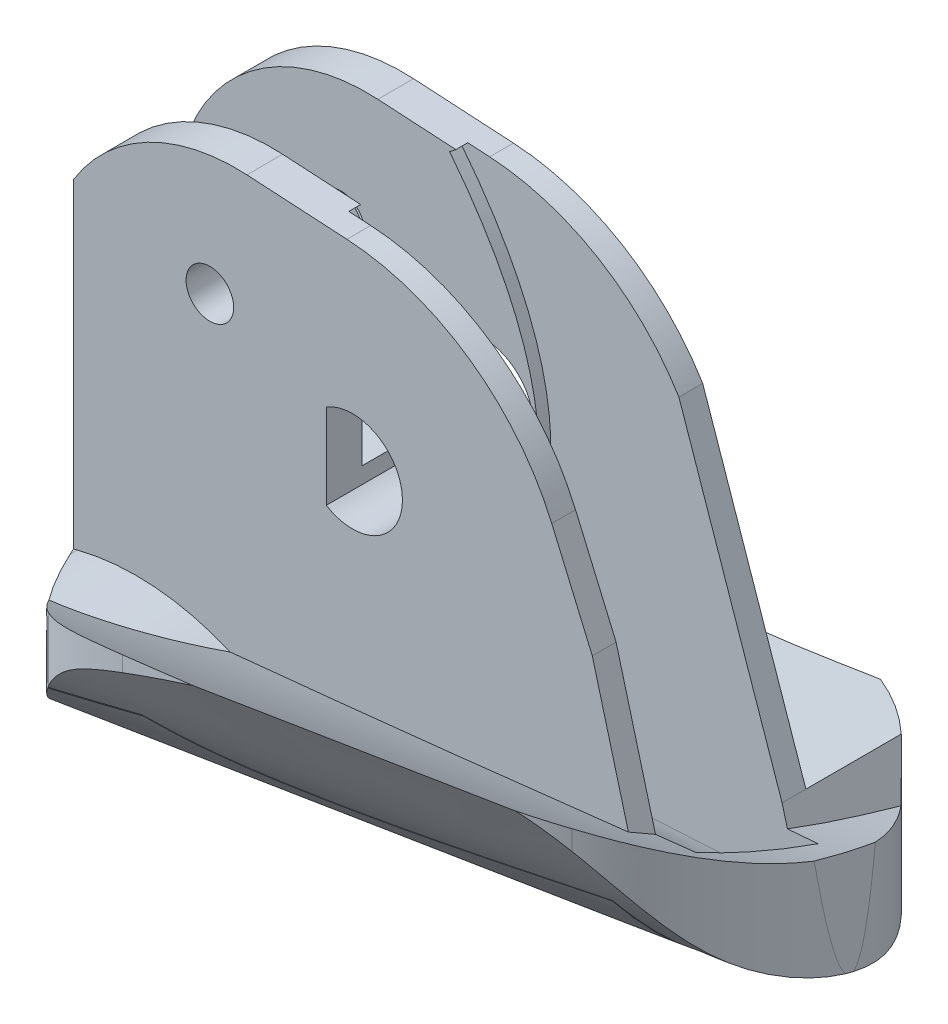
SolidWorks part; units mm, degrees
note: The reader was unsure of these and kept them because the rebuilt part matched: shared geometry of "Sketch11<2>".
ref_plane "Спереди" through (0, 0, 0) normal (0, 0, 1) x (1, 0, 0)
ref_plane "Сверху" through (0, 0, 0) normal (0, 1, 0) x (1, 0, 0)
ref_plane "Справа" through (0, 0, 0) normal (1, 0, 0) x (0, 0, -1)
sketch "Sketch5" plane through (0, 0, 0) normal (0, 0, 1) x (1, 0, 0)
  line L0 (1.7523, 0.4742) -> (37.3029, 86.8114) construction
  line L1 (-1.0106, -0.6044) -> (29.6618, 87.5839) construction
  line L2 (0, 0) -> (17.8901, 43.1295)
  line L3 (0, 0) -> (114.3643, 0) construction
  line L4 (23.8823, 39.6684) -> (24.5035, 51.2503)
  line B0 (17.4507, 115.16) -> (29.9551, 112.6983)
  spline B1 degree 3 poles (29.9551, 112.6983) (28.321, 116.0983) (27.9284, 121.1676) (30.1713, 134.4746) (29.8473, 132.0116) (30.6222, 139.9349) (27.0176, 140.9027) knots 0 0 0 0 0.297085 0.369784 0.687298 1 1 1 1
  spline B2 degree 2 poles (27.0176, 140.9027) (20.5603, 128.6427) (17.4507, 115.16) knots 0 0 0 1 1 1
  spline B3 degree 2 poles (27.0176, 140.9027) (26.5004, 134.6878) (22.2537, 130.5645) knots 0 0 0 1 1 1
  line B4 (17.1977, 114.3508) -> (29.842, 112.2111)
  line B5 (28.7001, 84.8969) -> (10.3668, 87.513)
  spline B6 degree 1 poles (17.1977, 114.3508) (10.3668, 87.513) knots 0 0 1 1
  spline B7 degree 2 poles (29.842, 112.2111) (22.5534, 98.8452) (28.7001, 84.8969) knots 0 0 0 1 1 1
  line B8 (10.1904, 87.4159) -> (28.2572, 84.4958)
  line B9 (32.8909, 45.7292) -> (10.0695, 42.8593)
  spline B10 degree 2 poles (10.1904, 87.4159) (10.0234, 65.1379) (10.0695, 42.8593) knots 0 0 0 1 1 1
  spline B11 degree 2 poles (28.2572, 84.4958) (20.6417, 64.1094) (32.8909, 45.7292) knots 0 0 0 1 1 1
  line B12 (10.2797, 36.8758) -> (3.9253, -13.9853)
  line B13 (3.9253, -13.9853) -> (33.9594, -31.0804)
  line B14 (33.9594, -31.0804) -> (45.9193, -27.7969)
  line B15 (45.9193, -27.7969) -> (58.2918, -13.9853)
  line B16 (58.2918, -13.9853) -> (69.0331, -4.9875)
  line B17 (69.0331, -4.9875) -> (82.514, 2.0236)
  line B18 (82.514, 2.0236) -> (89.2736, 3.8794)
  line B19 (89.2736, 3.8794) -> (92.4846, 9.5208)
  line B20 (92.4846, 9.5208) -> (96.8914, 17.263)
  line B21 (96.8914, 17.263) -> (101.4978, 21.1217)
  line B22 (101.4978, 21.1217) -> (103.9241, 23.1541)
  line B23 (104.261, 27.4157) -> (104.5375, 25.5318)
  line B24 (84.192, 21.2056) -> (87.7484, 22.7822)
  line B25 (87.7484, 22.7822) -> (92.912, 27.4956)
  line B26 (71.6086, 15.6268) -> (84.192, 21.2056)
  line B27 (92.912, 27.4956) -> (95.357, 29.7274)
  line B28 (95.357, 29.7274) -> (96.8049, 29.9399)
  line B29 (71.6086, 15.6268) -> (53.4239, 15.2713)
  line B30 (48.0904, 17.5622) -> (39.9394, 26.4919)
  line B31 (39.9394, 26.4919) -> (33.9594, 37.99)
  line B32 (33.9594, 37.99) -> (10.2797, 36.8758)
  line B33 (96.8049, 29.9399) -> (99.4078, 30.2175)
  line B34 (99.4078, 30.2175) -> (102.2786, 29.261)
  line B35 (102.2786, 29.261) -> (104.261, 27.4157)
  line B36 (104.5375, 25.5318) -> (103.9241, 23.1541)
  arc B37 (53.4239, 15.2713) -> (48.0904, 17.5622) centre (53.2864, 22.3051) cw
  spline B38 degree 3 poles (104.261, 27.4157) (103.5289, 27.0494) (99.8378, 26.2685) (94.8982, 17.2338) (98.6516, 18.7375) knots 0 0 0 0 0.441207 1 1 1 1
  line B39 (27.7375, 116.5129) -> (14.1959, 87.8955)
  line B40 (27.7375, 116.5129) -> (25.9485, 114.8372)
  line B41 (25.9485, 114.8372) -> (27.5763, 114.067)
  line B42 (27.7375, 116.5129) -> (27.5763, 114.067)
  line B43 (26.1527, 88.0864) -> (17.8901, 43.1295)
  line B44 (19.3622, 85.005) -> (23.8823, 39.6684)
  line B45 (19.3622, 85.005) -> (17.7584, 73.9508)
  line B46 (17.7584, 73.9508) -> (23.117, 74.485)
  line B47 (23.117, 74.485) -> (19.3622, 85.005)
  line B48 (26.1527, 88.0864) -> (23.7481, 82.7635)
  line B49 (23.7481, 82.7635) -> (25.1278, 82.5099)
  line B50 (25.1278, 82.5099) -> (26.5087, 82.2561)
  line B51 (26.5087, 82.2561) -> (26.1527, 88.0864)
  line B52 (26.1527, 88.0864) -> (19.3622, 85.005)
  line B53 (19.3622, 85.005) -> (22.3683, 87.7853)
  line B54 (22.3683, 87.7853) -> (22.9012, 86.6109)
  line B55 (22.9012, 86.6109) -> (23.4998, 85.2917)
  line B56 (23.4998, 85.2917) -> (19.3622, 85.005)
  dimension "D1" = 93.37
  dimension "D2" = 93.37
  dimension "D4" = 67.471
  dimension "D5" = 8.764
sketch_block_instance "Block1-1"
sketch_block "Block1"
sketch_block_instance "Block2-1"
sketch_block "Block2"
sketch_block_instance "Block3-1"
sketch_block "Block3"
sketch_block_instance "Block18-1"
sketch_block "Block18"
sketch_block_instance "Block44-1"
sketch_block "Block44"
sketch_block_instance "Block46-1"
sketch_block "Block46"
sketch_block_instance "Block47-1"
sketch_block "Block47"
sketch_block_instance "Block48-1"
sketch_block "Block48"
sketch_block_instance "Block50-1"
sketch_block "Block50"
sketch "Sketch10" plane through (0, 0, 0) normal (0, 0, 1) x (1, 0, 0)
  line L0 (29.8177, 47.6353) -> (33.9594, 37.99)
  line L3 (33.9594, 37.99) -> (36.9938, 26.6828)
  line L4 (22.7823, 39.6684) -> (22.7823, 41.4572)
  line L5 (22.7823, 39.6684) -> (22.7823, 37.8795)
  line L21 (10.2797, 36.8758) -> (12.7888, 23.6588)
  line L22 (12.7888, 23.6588) -> (36.9938, 26.6828)
  line L23 (10.2797, 36.8758) -> (12.3212, 48.6513)
  line L24 (12.3212, 48.6513) -> (29.8177, 47.6353)
  circle A0 centre (17.8901, 43.1295) radius 1
  arc A1 (22.7823, 37.8795) -> (22.7823, 41.4572) centre (23.8823, 39.6684) ccw
  spline S0 degree 3 poles (31.1276, 47.9087) (25.6896, 46.4972) (17.3791, 48.3877) (12.1681, 42.3773) knots 0.062609 0.062609 0.062609 0.062609 0.903704 0.903704 0.903704 0.903704 construction
  dimension "D1" = 4.2
  dimension "D2" = 2
extrude "Boss-Extrude5" add sketch "Sketch10" along normal mid plane 15
sketch "Sketch11" plane through (0, 0, 7.5) normal (0, 0, 1) x (1, 0, 0)
  line L0 (17.8254, 32.4239) -> (9.1237, 30.2079)
  line L1 (37.7529, 30.846) -> (34.6935, 60.2717)
  line L2 (34.6935, 60.2717) -> (6.5943, 53.1599)
  line L3 (6.5943, 53.1599) -> (9.1237, 30.2079)
  line L4 (37.7529, 30.846) -> (30.6791, 30.1551) construction
  line L5 (30.6791, 30.1551) -> (19.269, 26.7342) construction
  line L6 (19.269, 26.7342) -> (17.8254, 32.4239) construction
  line L7 (12.3212, 48.6513) -> (10.2797, 36.8758) construction
  spline S1 degree 3 poles (37.7529, 30.846) (30.6791, 30.1551) (19.269, 26.7342) (17.8254, 32.4239) knots 0 0 0 0 1 1 1 1
extrude "Cut-Extrude1" cut sketch "Sketch11" against normal blind 4
fillet "Fillet1" radius 10 1 edges at (29.8177, 47.6353, -2)
extrude "Cut-Extrude6" cut sketch "Sketch11<2>" against normal blind 10 from offset 11 offset against normal yes
sketch "Sketch11<2>" plane through (0, 0, 7.5) normal (0, 0, 1) x (1, 0, 0) same geometry as "Sketch11"
sketch "Sketch16" plane through (0, 0, 0) normal (0, 0, 1) x (1, 0, 0)
  line L1 (10.0743, 54.3608) -> (34.4186, 54.3608)
  line L2 (10.0743, 54.3608) -> (10.0743, 40.6451)
  line L3 (10.0743, 40.6451) -> (34.4186, 36.6644)
  line L4 (34.4186, 54.3608) -> (34.4186, 36.6644)
extrude "Cut-Extrude7" cut sketch "Sketch16" against normal mid plane 4
sketch "Sketch26" plane through (41.1882, 11.0532, 0) normal (0.9658, 0.2592, 0) x (0, 0, -1)
  line L12 (2, 27.8898) -> (2, 26.5356)
  line L13 (2, 26.5356) -> (-2, 26.5356)
  line L14 (-2, 26.5356) -> (-2, 27.8898)
  line L15 (-2, 27.8898) -> (-3.5, 27.8898)
  line L16 (-3.5, 27.8898) -> (-3.5, 20.2671)
  line L17 (-3.5, 20.2671) -> (-7.5, 20.2671)
  line L18 (-7.5, 20.2671) -> (-7.5, 16.1826)
  line L19 (-7.5, 16.1826) -> (7.5, 16.1826)
  line L20 (7.5, 16.1826) -> (7.5, 20.2671)
  line L21 (7.5, 20.2671) -> (3.5, 20.2671)
  line L22 (3.5, 20.2671) -> (3.5, 27.8898)
  line L23 (3.5, 27.8898) -> (2, 27.8898)
  line L24 (2, 27.8898) -> (2, 26.5356)
  line L25 (2, 26.5356) -> (-2, 26.5356)
  line L26 (-2, 26.5356) -> (-2, 27.8898)
  line L27 (-2, 27.8898) -> (-3.5, 27.8898)
  line L28 (-3.5, 27.8898) -> (-3.5, 20.2671)
  line L29 (-3.5, 20.2671) -> (-7.5, 20.2671)
  line L30 (-7.5, 20.2671) -> (-7.5, 16.1826)
  line L31 (-7.5, 16.1826) -> (7.5, 16.1826)
  line L32 (7.5, 16.1826) -> (7.5, 20.2671)
  line L33 (7.5, 20.2671) -> (3.5, 20.2671)
  line L34 (3.5, 20.2671) -> (3.5, 27.8898)
  line L35 (3.5, 27.8898) -> (2, 27.8898)
  dimension "D1" = 0
extrude "Boss-Extrude11" add sketch "Sketch26" along normal blind 9
sketch "Sketch28" plane through (-4.1944, 15.6296, 0) normal (0.2592, -0.9658, 0) x (0.9658, 0.2592, 0)
  line L0 (38.2441, 4.6151) -> (38.2441, -4.6151) construction
  line L1 (51.6455, 0) -> (42.6455, 0) construction
  line L2 (51.6455, 7.5) -> (51.6455, -7.5) construction
  line L3 (42.6455, 7.5) -> (42.6455, -7.5) construction
  circle A0 centre (38.2441, 4.6151) radius 1
  circle A1 centre (38.2441, -4.6151) radius 1
  point P10 (38.2441, 0)
  dimension "D1" = 2
sketch "Sketch32" plane through (49.8806, 13.3859, 0) normal (0.9658, 0.2592, 0) x (0, 0, -1)
  line L12 (3.5, 27.8898) -> (2, 27.8898)
  line L13 (2, 27.8898) -> (2, 26.5356)
  line L14 (2, 26.5356) -> (-2, 26.5356)
  line L15 (-2, 26.5356) -> (-2, 27.8898)
  line L16 (-2, 27.8898) -> (-3.5, 27.8898)
  line L17 (-3.5, 27.8898) -> (-3.5, 20.2671)
  line L18 (-3.5, 20.2671) -> (-7.5, 20.2671)
  line L19 (-7.5, 20.2671) -> (-7.5, 16.1826)
  line L20 (-7.5, 16.1826) -> (7.5, 16.1826)
  line L21 (7.5, 16.1826) -> (7.5, 20.2671)
  line L22 (7.5, 20.2671) -> (3.5, 20.2671)
  line L23 (3.5, 20.2671) -> (3.5, 27.8898)
  line L24 (3.5, 27.8898) -> (2, 27.8898)
  line L25 (2, 27.8898) -> (2, 26.5356)
  line L26 (2, 26.5356) -> (-2, 26.5356)
  line L27 (-2, 26.5356) -> (-2, 27.8898)
  line L28 (-2, 27.8898) -> (-3.5, 27.8898)
  line L29 (-3.5, 27.8898) -> (-3.5, 20.2671)
  line L30 (-3.5, 20.2671) -> (-7.5, 20.2671)
  line L31 (-7.5, 20.2671) -> (-7.5, 16.1826)
  line L32 (-7.5, 16.1826) -> (7.5, 16.1826)
  line L33 (7.5, 16.1826) -> (7.5, 20.2671)
  line L34 (7.5, 20.2671) -> (3.5, 20.2671)
  line L35 (3.5, 20.2671) -> (3.5, 27.8898)
  dimension "D1" = 0
extrude "Cut-Extrude9" cut sketch "Sketch32" against normal blind 9
fillet "Fillet2" radius 8 2 edges at (12.3212, 48.6513, 2.75) (12.3212, 48.6513, -2.75)
fillet "Fillet3" radius 10 2 edges at (17.8254, 32.4239, 5.5) (17.8254, 32.4239, -5.5)
sketch "Sketch33" plane through (0, 0, -7.5) normal (0, 0, -1) x (-1, 0, 0)
  line L8 (-11.4338, 30.7962) -> (-12.3264, 31.0236)
  line L9 (-35.9352, 30.6278) -> (-36.9938, 26.6828)
  line L10 (-36.9938, 26.6828) -> (-12.7888, 23.6588)
  line L15 (-12.7888, 23.6588) -> (-11.4338, 30.7962)
  line L16 (-11.4338, 30.7962) -> (-12.3264, 31.0236)
  line L17 (-35.9352, 30.6278) -> (-36.9938, 26.6828)
  line L18 (-36.9938, 26.6828) -> (-12.7888, 23.6588)
  line L23 (-12.7888, 23.6588) -> (-11.4338, 30.7962)
  arc A1 (-12.3264, 31.0236) -> (-19.6523, 30.0735) centre (-14.7943, 21.3329) ccw
  arc A2 (-12.3264, 31.0236) -> (-19.6523, 30.0735) centre (-14.7943, 21.3329) ccw
  spline S1 degree 3 poles (-2248.4451, 2036.9138) (2398.2149, -1976.4492) (-2488.6024, 2006.9679) (2269.0143, -1889.1309) knots -4.784802 -4.784802 -4.784802 -4.784802 6.242241 6.242241 6.242241 6.242241 only from (-19.6523, 30.0735) to (-35.9352, 30.6278)
  spline S2 degree 3 poles (-19.6523, 30.0735) (-23.0941, 28.1606) (-30.3498, 29.8586) (-35.9352, 30.6278) knots 0.191602 0.191602 0.191602 0.191602 0.918086 0.918086 0.918086 0.918086
  dimension "D1" = 0
extrude "Boss-Extrude15" add sketch "Sketch33" along normal blind 2
ref_plane "Plane1" through (38.4615, 25.5911, -2.6463) normal (-0.987, -0.0285, 0.1584) x (0.1583, 0.0046, 0.9874)
sketch "Sketch34" plane through (38.4615, 25.5911, -2.6463) normal (-0.987, -0.0285, 0.1584) x (0.1583, 0.0046, 0.9874)
  line L1 (-9.9613, -0.7387) -> (-10.5398, -8.5297)
  line L3 (-10.5398, -8.5297) -> (14.0671, -4.6342)
  line L4 (14.0671, -4.6342) -> (11.4688, 6.9569)
  line L5 (11.4688, 6.9569) -> (11.2103, 7.3048)
  line L6 (9.3619, 9.0979) -> (11.2103, 7.3048)
  spline S1 degree 3 poles (9.3619, 9.0979) (8.0808, 7.1287) (6.1822, 3.4329) (1.2126, 0.2397) (-4.0234, -1.2627) (-7.9896, -1.4142) (-9.9613, -0.7387) knots 0 0 0 0 0.305307 0.51081 0.734727 1 1 1 1
extrude "Cut-Extrude10" cut sketch "Sketch34" along normal blind 39
sketch "Sketch35" plane through (38.4615, 25.5911, -2.6463) normal (-0.987, -0.0285, 0.1584) x (0.1583, 0.0046, 0.9874)
  line L0 (9.4005, 9.1848) -> (3.3279, 5.0721) construction
  line L1 (3.3279, 5.0721) -> (-2.7348, 1.7749) construction
  line L2 (-2.7348, 1.7749) -> (-13.1414, 3.4012) construction
  line L5 (-13.1414, 3.4012) -> (-9.5787, -0.8831) construction
  spline S0 degree 3 poles (9.4005, 9.1848) (8.0149, 7.019) (5.8425, 2.8785) (-1.139, -0.8866) (-6.3054, -1.5967) (-9.5787, -0.8831) knots 0 0 0 0 0.341444 0.573298 1 1 1 1
  spline S1 degree 3 poles (6.8156, 5.1075) (6.3414, 4.4434) (5.0935, 2.8969) (3.4618, 1.7144) (2.4324, 1.1336) knots 0.201432 0.201432 0.201432 0.201432 0.305307 0.455135 0.455135 0.455135 0.455135 construction
  spline S2 degree 3 poles (-5.3799, -1.1913) (-4.8408, -1.1453) (-2.5388, -0.8367) (0.0833, -0.0843) (2.0499, 0.9178) (2.4324, 1.1336) knots 0.196975 0.196975 0.196975 0.196975 0.265273 0.48919 0.544865 0.544865 0.544865 0.544865 construction
  spline S3 degree 4 poles (9.4005, 9.1848) (3.3279, 5.0721) (-2.7348, 1.7749) (-13.1414, 3.4012) (-9.5787, -0.8831) knots 0 0 0 0 0 1 1 1 1 1
extrude "Boss-Extrude16" add sketch "Sketch35" along normal blind 35
sketch "Sketch36" plane through (0, 0, 0) normal (0, 1, 0) x (1, 0, 0)
  line L0 (22.2747, 9.702) -> (19.2802, 8.5421)
  circle A0 centre (26.2258, -0.6503) radius 26.4347
  arc A1 (32.0453, -8.6033) -> (26.2258, -9.3573) centre (2192.8185, -16707.6767) ccw
  spline S27 degree 3 poles (27.8922, 10.6475) (26.9334, 10.6337) (25.9886, 10.5289) (24.5845, 10.2862) (24.1189, 10.1901) (23.1921, 9.9682) (22.73, 9.842) (22.2747, 9.702) knots 0 0 0 0 0.5 0.5 0.75 0.75 1 1 1 1
  spline S29 degree 3 poles (19.2802, 8.5421) (18.1759, 8.0221) (17.1049, 7.4097) (15.0752, 6.0455) (14.1101, 5.2944) (13.1983, 4.4671) knots 0 0 0 0 0.5 0.5 1 1 1 1
  spline S30 degree 3 poles (13.1983, 4.4671) (12.8563, 4.1568) (12.5211, 3.838) (12.0629, 3.3185) (11.9182, 3.1375) (11.6617, 2.757) (11.5505, 2.5565) (11.4557, 2.346) knots 0 0 0 0 0.5 0.5 0.75 0.75 1 1 1 1
  spline S31 degree 3 poles (11.4557, 2.346) (11.284, 1.9646) (11.1649, 1.5649) (11.0081, 0.7554) (10.9712, 0.3454) (10.9879, -0.0592) knots 0 0 0 0 0.5 0.5 1 1 1 1
  spline S32 degree 3 poles (10.9879, -0.0592) (10.9979, -0.3025) (11.0294, -0.5425) (11.1263, -1.0087) (11.1909, -1.2366) (11.4103, -1.9049) (11.5882, -2.33) (11.7801, -2.7383) knots 0 0 0 0 0.25 0.25 0.5 0.5 1 1 1 1
  spline S33 degree 3 poles (11.7801, -2.7383) (11.9136, -3.0221) (12.0539, -3.2973) (12.1957, -3.5663) knots 0 0 0 0 1 1 1 1
  spline S34 degree 3 poles (12.1957, -3.5663) (12.4115, -3.9755) (12.6305, -4.3688) (13.0779, -5.1243) (13.3054, -5.4845) (13.7845, -6.1648) (14.0386, -6.4847) (14.5871, -7.0709) (14.8803, -7.3391) (15.1896, -7.5863) knots 0 0 0 0 0.25 0.25 0.5 0.5 0.75 0.75 1 1 1 1
  spline S35 degree 3 poles (15.1896, -7.5863) (15.4845, -7.8221) (15.7909, -8.0364) (16.4511, -8.4118) (16.8052, -8.5727) (17.6001, -8.8248) (18.0301, -8.9109) (18.9251, -9.0401) (19.3853, -9.0839) (19.8478, -9.1216) knots 0 0 0 0 0.25 0.25 0.5 0.5 0.75 0.75 1 1 1 1
  spline S36 degree 3 poles (19.8478, -9.1216) (20.3759, -9.1646) (20.9057, -9.2003) (21.9634, -9.2645) (22.4923, -9.2916) (24.0799, -9.3576) (25.1387, -9.3807) (26.2258, -9.3573) knots 0 0 0 0 0.25 0.25 0.5 0.5 1 1 1 1
  spline S37 degree 3 poles (32.0453, -8.6033) (32.4849, -8.4754) (32.895, -8.3314) (33.6607, -8.0097) (34.0089, -7.8361) (34.332, -7.6481) knots 0 0 0 0 0.5 0.5 1 1 1 1
  spline S38 degree 3 poles (34.332, -7.6481) (34.9868, -7.2672) (35.5151, -6.84) (35.9629, -6.3477) knots 0 0 0 0 1 1 1 1
  spline S39 degree 3 poles (35.9629, -6.3477) (36.2177, -6.0676) (36.4446, -5.7715) (36.8644, -5.1443) (37.0562, -4.8132) (37.4091, -4.1124) (37.5701, -3.7428) (37.8622, -2.9604) (37.9936, -2.5457) (38.2178, -1.6879) (38.3115, -1.2432) (38.457, -0.321) (38.5089, 0.1566) (38.5454, 0.8995) (38.5505, 1.1526) (38.5441, 1.661) (38.5326, 1.9167) (38.4691, 2.6875) (38.3891, 3.2062) (38.185, 3.9872) (38.1026, 4.2476) (37.9091, 4.7535) (37.7978, 5.0008) (37.5471, 5.4841) (37.4078, 5.7202) (37.102, 6.1813) (36.9347, 6.4071) (36.4059, 7.0544) (36.0151, 7.4506) (35.1713, 8.185) (34.7172, 8.5233) (33.7779, 9.1303) (33.2898, 9.4021) (32.5283, 9.7588) (32.2684, 9.8696) (31.743, 10.0689) (31.4778, 10.1573) (30.6747, 10.3882) (30.1294, 10.4966) (29.0203, 10.6303) (28.4554, 10.6556) (27.8922, 10.6475) knots 0 0 0 0 0.0625 0.0625 0.125 0.125 0.1875 0.1875 0.25 0.25 0.3125 0.3125 0.375 0.375 0.40625 0.40625 0.4375 0.4375 0.5 0.5 0.53125 0.53125 0.5625 0.5625 0.59375 0.59375 0.625 0.625 0.6875 0.6875 0.75 0.75 0.8125 0.8125 0.84375 0.84375 0.875 0.875 0.9375 0.9375 1 1 1 1
extrude "Cut-Extrude11" cut sketch "Sketch36" along normal blind 50
sketch "Sketch37" plane through (0, 0, 0) normal (0, 1, 0) x (1, 0, 0)
  circle A0 centre (31.6606, 4.5) radius 1
  circle A1 centre (31.6606, -4.5) radius 1
  dimension "D1" = 2
sketch "Sketch38" plane through (0, 0, 0) normal (0, 0, 1) x (1, 0, 0)
  line L0 (25.6305, 35.1974) -> (28.424, 17.492)
  line L1 (28.424, 17.492) -> (38.6586, 12.2021)
  line L2 (38.6586, 12.2021) -> (36.1416, 49.0283)
  line L3 (36.1416, 49.0283) -> (23.9734, 49.0283)
  line L4 (22.4652, 47.8412) -> (27.7083, 41.1798) construction
  line L5 (27.7083, 41.1798) -> (25.6305, 35.1974) construction
  line L6 (23.9734, 49.0283) -> (22.4652, 47.8412)
  spline S0 degree 2 poles (22.4652, 47.8412) (27.7083, 41.1798) (25.6305, 35.1974) knots 0 0 0 1 1 1
extrude "Cut-Extrude13" cut sketch "Sketch38" against normal mid plane 5
fillet "Fillet5" radius 3 1 edges
sketch "Sketch39" plane through (0, 0, -3.5) normal (0, 0, -1) x (-1, 0, 0)
  line L0 (-31.1496, 44.5336) -> (-35.9352, 30.6278)
  line L1 (-32.2564, 41.9561) -> (-33.9594, 37.99) construction
  line L2 (-35.9352, 30.6278) -> (-33.9594, 37.99)
  line L3 (-33.9594, 37.99) -> (-31.1496, 44.5336)
extrude "Cut-Extrude14" cut sketch "Sketch39" against normal blind 2
sketch "Sketch40" plane through (0, 0, 2.5) normal (0, 0, -1) x (-1, 0, 0)
  line L0 (-28.8475, 43.6873) -> (-28.2997, 34.3422)
  line L2 (-28.8475, 43.6873) -> (-33.9594, 37.99)
  line L3 (-33.9594, 37.99) -> (-34.7872, 34.9054)
  line L4 (-33.9594, 37.99) -> (-35.615, 31.8208) construction
  line L6 (-35.615, 31.8208) -> (-28.2997, 34.3422)
  line L7 (-34.7872, 34.9054) -> (-35.615, 31.8208)
